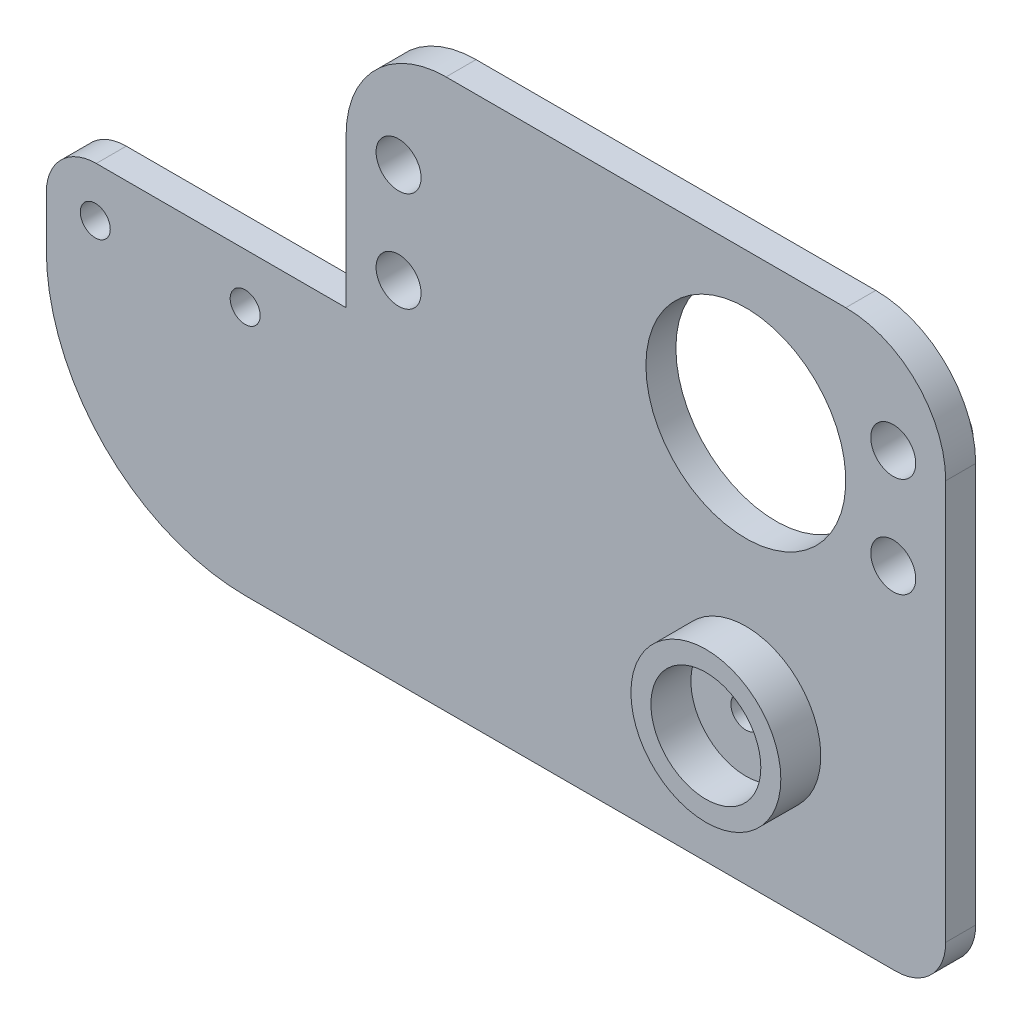
SolidWorks part; units mm, degrees
ref_plane "前视基准面" through (0, 0, 0) normal (0, 0, 1) x (1, 0, 0)
ref_plane "上视基准面" through (0, 0, 0) normal (0, 1, 0) x (1, 0, 0)
ref_plane "右视基准面" through (0, 0, 0) normal (1, 0, 0) x (0, 0, -1)
sketch "草图3" plane through (0, 0, 0) normal (0, 0, 1) x (1, 0, 0)
  line L0 (60.2665, 6.5325) -> (60.2665, 16.5325)
  line L1 (10.7665, 16.5325) -> (10.7665, 6.5325)
  line L2 (10.7665, 16.5325) -> (60.2665, 16.5325)
  circle A0 centre (60.2665, 16.5325) radius 3
  circle A1 centre (60.2665, 6.5325) radius 3
  circle A6 centre (10.7665, 6.5325) radius 3
  circle A7 centre (10.7665, 16.5325) radius 3
  dimension "D1" = 6
  dimension "D2" = 6
  dimension "D4" = 6
  dimension "D5" = 6
  dimension "D3" = 10
  dimension "D6" = 49.5
  dimension "D7" = 49.5
  dimension "D8" = 10
extrude "凸台-拉伸6" add sketch "草图3" along normal blind 2 contours A6 | A0 | A1 | A7
sketch "草图11" plane through (0, 0, 2) normal (0, 0, 1) x (1, 0, 0)
  circle A0 centre (10.7665, 16.5325) radius 2.25
  circle A1 centre (10.7665, 6.5325) radius 2.25
  circle A2 centre (60.2665, 16.5325) radius 2.25
  circle A3 centre (60.2665, 6.5325) radius 2.25
  dimension "D1" = 4.5
  dimension "D2" = 4.5
  dimension "D3" = 4.5
  dimension "D4" = 4.5
extrude "切除-拉伸2" cut sketch "草图11" against normal blind 2 and the other way blind 10
sketch "草图12" plane through (0, 0, 2) normal (0, 0, 1) x (1, 0, 0)
  line L4 (10.7665, 16.5325) -> (60.2665, 6.5325) construction
  line L5 (10.7665, 6.5325) -> (60.2665, 16.5325) construction
  line L6 (60.2665, 16.5325) -> (60.2665, 6.5325) construction
  line L7 (5.5165, 26.5325) -> (65.5165, 26.5325)
  line L8 (5.5165, 26.5325) -> (5.5165, 1.5325)
  line L9 (5.5165, -28.4675) -> (65.5165, -28.4675)
  line L10 (65.5165, 26.5325) -> (65.5165, -28.4675)
  line L11 (5.5165, 1.5325) -> (5.5165, -28.4675) construction
  line L12 (5.5165, -28.4675) -> (-24.4835, -28.4675)
  line L13 (5.5165, -28.4675) -> (5.5165, 1.5325) construction
  line L14 (5.5165, 1.5325) -> (-24.4835, 1.5325)
  line L15 (-24.4835, -28.4675) -> (-24.4835, 1.5325)
  circle A4 centre (45.5165, 11.5325) radius 10
  point P8 (35.5165, 11.5325)
  point P9 (35.5165, 26.5325)
  point P10 (-46.6091, 14.6442)
  point P11 (60.2665, 11.5325)
  dimension "D5" = 20
  dimension "D1" = 60
  dimension "D2" = 55
  dimension "D3" = 15
  dimension "D4" = 14.75
  dimension "D6" = 30
  dimension "D7" = 30
extrude "凸台-拉伸7" add sketch "草图12" along normal blind 3 contours L7 L10 L9 L12 L15 L14 L8
sketch "草图14" plane through (0, 0, 2) normal (0, 0, -1) x (-1, 0, 0)
  line L0 (-60.2665, 16.5325) -> (-60.2665, 6.5325) construction
  circle A0 centre (-60.2665, 6.5325) radius 2.25 construction
  circle A1 centre (-60.2665, 6.5325) radius 2.25
  circle A2 centre (-60.2665, 16.5325) radius 2.25 construction
  circle A3 centre (-60.2665, 16.5325) radius 2.25
  circle A4 centre (-10.7665, 6.5325) radius 2.25 construction
  circle A5 centre (-10.7665, 16.5325) radius 2.25 construction
  circle A6 centre (-10.7665, 6.5325) radius 2.25
  circle A7 centre (-10.7665, 16.5325) radius 2.25
  circle A8 centre (-45.5165, 11.5325) radius 10
  point P14 (-60.2665, 11.5325)
  point P15 (0.1696, -0.033)
  dimension "D2" = 20
  dimension "D1" = 14.75
extrude "切除-拉伸3" cut sketch "草图14" against normal blind 3
sketch "草图15" plane through (0, 0, 2) normal (0, 0, -1) x (-1, 0, 0)
  circle A0 centre (-45.5165, 11.5325) radius 10 construction
  circle A1 centre (-45.5165, 11.5325) radius 10
  circle A2 centre (-45.5165, -13.5675) radius 1.5
  dimension "D2" = 3
  dimension "D1" = 25.1
extrude "切除-拉伸4" cut sketch "草图15" against normal blind 3
fillet "圆角3" radius 5 2 edges at (65.5165, -28.4675, 3.5) (-24.4835, 1.5325, 3.5)
fillet "圆角4" radius 10 2 edges at (65.5165, 26.5325, 3.5) (5.5165, 26.5325, 3.5)
sketch "草图16" plane through (0, 0, 5) normal (0, 0, 1) x (1, 0, 0)
  line L6 (5.5165, 16.5325) -> (5.5165, 1.5325) construction
  line L7 (-24.4835, -28.4675) -> (60.5165, -28.4675) construction
  circle A0 centre (-19.5835, -3.4675) radius 1.5
  circle A1 centre (-4.5835, -3.4675) radius 1.5
  dimension "D1" = 3
  dimension "D2" = 25.1
  dimension "D3" = 25
  dimension "D5" = 15
  dimension "D4" = 2
extrude "切除-拉伸5" cut sketch "草图16" against normal blind 10
fillet "圆角5" radius 20 1 edges at (-24.4835, -28.4675, 3.5)
sketch "草图17" plane through (0, 0, 5) normal (0, 0, 1) x (1, 0, 0)
  circle A0 centre (45.5165, -13.5675) radius 7.5
  circle A1 centre (45.5165, -13.5675) radius 5.5
  dimension "D1" = 15
  dimension "D2" = 2
extrude "凸台-拉伸8" add sketch "草图17" along normal blind 4
